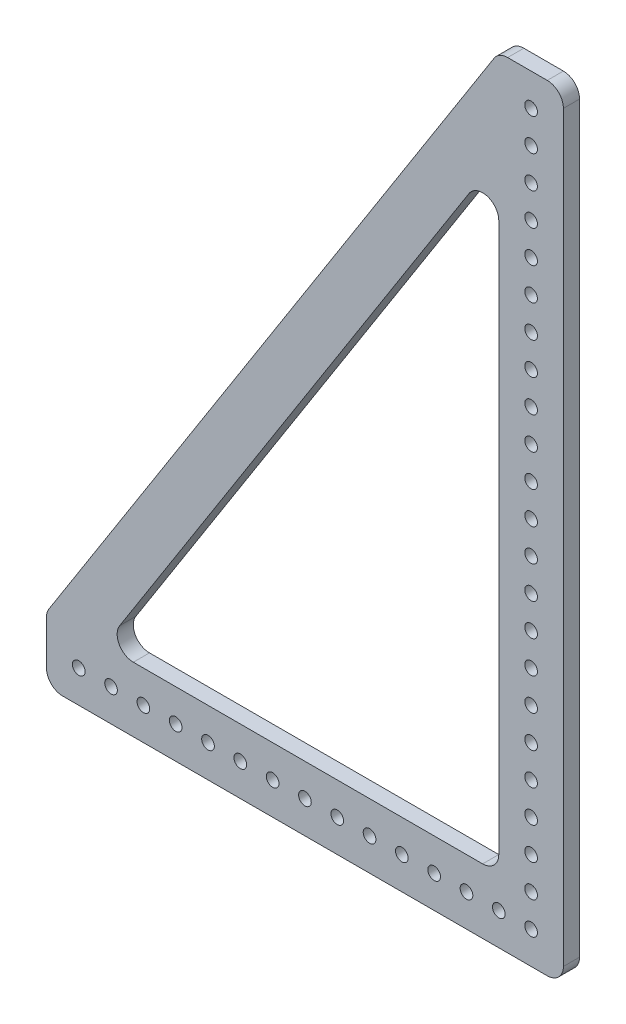
SolidWorks part; units mm, degrees
material "6061-T6 (SS)"
ref_plane "Front Plane" through (0, 0, 0) normal (0, 0, 1) x (1, 0, 0)
ref_plane "Top Plane" through (0, 0, 0) normal (0, 1, 0) x (1, 0, 0)
ref_plane "Right Plane" through (0, 0, 0) normal (1, 0, 0) x (0, 0, -1)
sketch "Sketch1" plane through (0, 0, 0) normal (0, 0, 1) x (1, 0, 0)
  line L0 (0, 25.4) -> (177.8, 304.8)
  line L1 (177.8, 304.8) -> (203.2, 304.8)
  line L2 (0, 25.4) -> (0, 0)
  line L3 (0, 0) -> (203.2, 0)
  line L4 (203.2, 304.8) -> (203.2, 0)
  dimension "D1" = 304.8
  dimension "D2" = 203.2
  dimension "D3" = 25.4
  dimension "D4" = 25.4
extrude "Boss-Extrude1" add sketch "Sketch1" along normal blind 6.35
sketch "Sketch2" plane through (0, 0, 6.35) normal (0, 0, 1) x (1, 0, 0)
  line L0 (0, 0) -> (203.2, 0) construction
  line L1 (203.2, 0) -> (203.2, 304.8) construction
  line L2 (22.5801, 25.4) -> (177.8, 25.4)
  line L3 (177.8, 25.4) -> (177.8, 269.3169)
  line L4 (177.8, 269.3169) -> (22.5801, 25.4)
  line L5 (177.8, 304.8) -> (0, 25.4) construction
  circle A0 centre (190.5, 12.7) radius 2.4892
  circle A1 centre (177.8, 12.7) radius 2.4892
  circle A2 centre (165.1, 12.7) radius 2.4892
  circle A3 centre (152.4, 12.7) radius 2.4892
  circle A4 centre (139.7, 12.7) radius 2.4892
  circle A5 centre (127, 12.7) radius 2.4892
  circle A6 centre (114.3, 12.7) radius 2.4892
  circle A67 centre (190.5, 25.4) radius 2.4892
  circle A68 centre (190.5, 38.1) radius 2.4892
  circle A69 centre (190.5, 50.8) radius 2.4892
  circle A70 centre (190.5, 63.5) radius 2.4892
  circle A71 centre (190.5, 76.2) radius 2.4892
  circle A72 centre (190.5, 88.9) radius 2.4892
  circle A73 centre (190.5, 101.6) radius 2.4892
  circle A74 centre (190.5, 114.3) radius 2.4892
  circle A75 centre (190.5, 127) radius 2.4892
  circle A76 centre (190.5, 139.7) radius 2.4892
  circle A77 centre (190.5, 152.4) radius 2.4892
  circle A84 centre (190.5, 165.1) radius 2.4892
  circle A91 centre (190.5, 177.8) radius 2.4892
  circle A98 centre (190.5, 190.5) radius 2.4892
  circle A105 centre (190.5, 203.2) radius 2.4892
  circle A112 centre (190.5, 215.9) radius 2.4892
  circle A119 centre (190.5, 228.6) radius 2.4892
  circle A126 centre (190.5, 241.3) radius 2.4892
  circle A133 centre (190.5, 254) radius 2.4892
  circle A140 centre (190.5, 266.7) radius 2.4892
  circle A147 centre (190.5, 279.4) radius 2.4892
  circle A154 centre (190.5, 292.1) radius 2.4892
  circle A161 centre (177.8, 152.4) radius 2.4892 [skipped]
  circle A162 centre (165.1, 152.4) radius 2.4892 [skipped]
  circle A163 centre (152.4, 152.4) radius 2.4892 [skipped]
  circle A164 centre (139.7, 152.4) radius 2.4892 [skipped]
  circle A165 centre (127, 152.4) radius 2.4892 [skipped]
  circle A166 centre (114.3, 152.4) radius 2.4892 [skipped]
  circle A167 centre (177.8, 165.1) radius 2.4892 [skipped]
  circle A168 centre (165.1, 165.1) radius 2.4892 [skipped]
  circle A169 centre (152.4, 165.1) radius 2.4892 [skipped]
  circle A170 centre (139.7, 165.1) radius 2.4892 [skipped]
  circle A171 centre (127, 165.1) radius 2.4892 [skipped]
  circle A172 centre (114.3, 165.1) radius 2.4892 [skipped]
  circle A173 centre (177.8, 177.8) radius 2.4892 [skipped]
  circle A174 centre (165.1, 177.8) radius 2.4892 [skipped]
  circle A175 centre (152.4, 177.8) radius 2.4892 [skipped]
  circle A176 centre (139.7, 177.8) radius 2.4892 [skipped]
  circle A177 centre (127, 177.8) radius 2.4892 [skipped]
  circle A178 centre (114.3, 177.8) radius 2.4892 [skipped]
  circle A179 centre (177.8, 190.5) radius 2.4892 [skipped]
  circle A180 centre (165.1, 190.5) radius 2.4892 [skipped]
  circle A181 centre (152.4, 190.5) radius 2.4892 [skipped]
  circle A182 centre (139.7, 190.5) radius 2.4892 [skipped]
  circle A183 centre (127, 190.5) radius 2.4892 [skipped]
  circle A184 centre (114.3, 190.5) radius 2.4892 [skipped]
  circle A185 centre (177.8, 203.2) radius 2.4892 [skipped]
  circle A186 centre (165.1, 203.2) radius 2.4892 [skipped]
  circle A187 centre (152.4, 203.2) radius 2.4892 [skipped]
  circle A188 centre (139.7, 203.2) radius 2.4892 [skipped]
  circle A189 centre (127, 203.2) radius 2.4892 [skipped]
  circle A190 centre (114.3, 203.2) radius 2.4892 [skipped]
  circle A191 centre (177.8, 215.9) radius 2.4892 [skipped]
  circle A192 centre (165.1, 215.9) radius 2.4892 [skipped]
  circle A193 centre (152.4, 215.9) radius 2.4892 [skipped]
  circle A194 centre (139.7, 215.9) radius 2.4892 [skipped]
  circle A195 centre (127, 215.9) radius 2.4892 [skipped]
  circle A196 centre (114.3, 215.9) radius 2.4892 [skipped]
  circle A197 centre (177.8, 228.6) radius 2.4892 [skipped]
  circle A198 centre (165.1, 228.6) radius 2.4892 [skipped]
  circle A199 centre (152.4, 228.6) radius 2.4892 [skipped]
  circle A200 centre (139.7, 228.6) radius 2.4892 [skipped]
  circle A201 centre (127, 228.6) radius 2.4892 [skipped]
  circle A202 centre (114.3, 228.6) radius 2.4892 [skipped]
  circle A203 centre (177.8, 241.3) radius 2.4892 [skipped]
  circle A204 centre (165.1, 241.3) radius 2.4892 [skipped]
  circle A205 centre (152.4, 241.3) radius 2.4892 [skipped]
  circle A206 centre (139.7, 241.3) radius 2.4892 [skipped]
  circle A207 centre (127, 241.3) radius 2.4892 [skipped]
  circle A208 centre (114.3, 241.3) radius 2.4892 [skipped]
  circle A209 centre (177.8, 254) radius 2.4892 [skipped]
  circle A210 centre (165.1, 254) radius 2.4892 [skipped]
  circle A211 centre (152.4, 254) radius 2.4892 [skipped]
  circle A212 centre (139.7, 254) radius 2.4892 [skipped]
  circle A213 centre (127, 254) radius 2.4892 [skipped]
  circle A214 centre (114.3, 254) radius 2.4892 [skipped]
  circle A215 centre (177.8, 266.7) radius 2.4892 [skipped]
  circle A216 centre (165.1, 266.7) radius 2.4892 [skipped]
  circle A217 centre (152.4, 266.7) radius 2.4892 [skipped]
  circle A218 centre (139.7, 266.7) radius 2.4892 [skipped]
  circle A219 centre (127, 266.7) radius 2.4892 [skipped]
  circle A220 centre (114.3, 266.7) radius 2.4892 [skipped]
  circle A221 centre (177.8, 279.4) radius 2.4892 [skipped]
  circle A222 centre (165.1, 279.4) radius 2.4892 [skipped]
  circle A223 centre (152.4, 279.4) radius 2.4892 [skipped]
  circle A224 centre (139.7, 279.4) radius 2.4892 [skipped]
  circle A225 centre (127, 279.4) radius 2.4892 [skipped]
  circle A226 centre (114.3, 279.4) radius 2.4892 [skipped]
  circle A227 centre (177.8, 292.1) radius 2.4892 [skipped]
  circle A228 centre (165.1, 292.1) radius 2.4892 [skipped]
  circle A229 centre (152.4, 292.1) radius 2.4892 [skipped]
  circle A230 centre (139.7, 292.1) radius 2.4892 [skipped]
  circle A231 centre (127, 292.1) radius 2.4892 [skipped]
  circle A232 centre (114.3, 292.1) radius 2.4892 [skipped]
  circle A233 centre (165.1, 25.4) radius 2.4892 construction
  circle A234 centre (152.4, 25.4) radius 2.4892 construction
  circle A235 centre (139.7, 25.4) radius 2.4892 construction
  circle A236 centre (127, 25.4) radius 2.4892 construction
  circle A237 centre (114.3, 25.4) radius 2.4892 construction
  circle A238 centre (177.8, 38.1) radius 2.4892 construction
  circle A239 centre (165.1, 38.1) radius 2.4892 construction
  circle A240 centre (152.4, 38.1) radius 2.4892 construction
  circle A241 centre (139.7, 38.1) radius 2.4892 construction
  circle A242 centre (127, 38.1) radius 2.4892 construction
  circle A243 centre (114.3, 38.1) radius 2.4892 construction
  circle A244 centre (177.8, 50.8) radius 2.4892 construction
  circle A245 centre (165.1, 50.8) radius 2.4892 construction
  circle A246 centre (152.4, 50.8) radius 2.4892 construction
  circle A247 centre (139.7, 50.8) radius 2.4892 construction
  circle A248 centre (127, 50.8) radius 2.4892 construction
  circle A249 centre (114.3, 50.8) radius 2.4892 construction
  circle A250 centre (177.8, 63.5) radius 2.4892 construction
  circle A251 centre (165.1, 63.5) radius 2.4892 construction
  circle A252 centre (152.4, 63.5) radius 2.4892 construction
  circle A253 centre (139.7, 63.5) radius 2.4892 construction
  circle A254 centre (127, 63.5) radius 2.4892 construction
  circle A255 centre (114.3, 63.5) radius 2.4892 construction
  circle A256 centre (177.8, 76.2) radius 2.4892 construction
  circle A257 centre (165.1, 76.2) radius 2.4892 construction
  circle A258 centre (152.4, 76.2) radius 2.4892 construction
  circle A259 centre (139.7, 76.2) radius 2.4892 construction
  circle A260 centre (127, 76.2) radius 2.4892 construction
  circle A261 centre (114.3, 76.2) radius 2.4892 construction
  circle A262 centre (177.8, 88.9) radius 2.4892 construction
  circle A263 centre (165.1, 88.9) radius 2.4892 construction
  circle A264 centre (152.4, 88.9) radius 2.4892 construction
  circle A265 centre (139.7, 88.9) radius 2.4892 construction
  circle A266 centre (127, 88.9) radius 2.4892 construction
  circle A267 centre (114.3, 88.9) radius 2.4892 construction
  circle A268 centre (177.8, 101.6) radius 2.4892 construction
  circle A269 centre (165.1, 101.6) radius 2.4892 construction
  circle A270 centre (152.4, 101.6) radius 2.4892 construction
  circle A271 centre (139.7, 101.6) radius 2.4892 construction
  circle A272 centre (127, 101.6) radius 2.4892 construction
  circle A273 centre (114.3, 101.6) radius 2.4892 construction
  circle A274 centre (177.8, 114.3) radius 2.4892 construction
  circle A275 centre (165.1, 114.3) radius 2.4892 construction
  circle A276 centre (152.4, 114.3) radius 2.4892 construction
  circle A277 centre (139.7, 114.3) radius 2.4892 construction
  circle A278 centre (127, 114.3) radius 2.4892 construction
  circle A279 centre (114.3, 114.3) radius 2.4892 construction
  circle A280 centre (177.8, 127) radius 2.4892 construction
  circle A281 centre (165.1, 127) radius 2.4892 construction
  circle A282 centre (152.4, 127) radius 2.4892 construction
  circle A283 centre (139.7, 127) radius 2.4892 construction
  circle A284 centre (127, 127) radius 2.4892 construction
  circle A285 centre (114.3, 127) radius 2.4892 construction
  circle A286 centre (177.8, 139.7) radius 2.4892 construction
  circle A287 centre (165.1, 139.7) radius 2.4892 construction
  circle A288 centre (152.4, 139.7) radius 2.4892 construction
  circle A289 centre (139.7, 139.7) radius 2.4892 construction
  circle A290 centre (127, 139.7) radius 2.4892 construction
  circle A291 centre (114.3, 139.7) radius 2.4892 construction
  circle A292 centre (177.8, 25.4) radius 2.4892 construction
  circle A293 centre (101.6, 12.7) radius 2.4892
  circle A294 centre (88.9, 12.7) radius 2.4892
  circle A295 centre (76.2, 12.7) radius 2.4892
  circle A296 centre (63.5, 12.7) radius 2.4892
  circle A297 centre (50.8, 12.7) radius 2.4892
  circle A298 centre (38.1, 12.7) radius 2.4892
  circle A299 centre (25.4, 12.7) radius 2.4892
  circle A300 centre (12.7, 12.7) radius 2.4892
  circle A477 centre (101.6, 25.4) radius 2.4892 [skipped]
  circle A478 centre (88.9, 25.4) radius 2.4892 [skipped]
  circle A479 centre (76.2, 25.4) radius 2.4892 [skipped]
  circle A480 centre (63.5, 25.4) radius 2.4892 [skipped]
  circle A481 centre (50.8, 25.4) radius 2.4892 [skipped]
  circle A482 centre (38.1, 25.4) radius 2.4892 [skipped]
  circle A483 centre (25.4, 25.4) radius 2.4892 [skipped]
  circle A484 centre (12.7, 25.4) radius 2.4892 [skipped]
  circle A485 centre (101.6, 38.1) radius 2.4892 [skipped]
  circle A486 centre (88.9, 38.1) radius 2.4892 [skipped]
  circle A487 centre (76.2, 38.1) radius 2.4892 [skipped]
  circle A488 centre (63.5, 38.1) radius 2.4892 [skipped]
  circle A489 centre (50.8, 38.1) radius 2.4892 [skipped]
  circle A490 centre (38.1, 38.1) radius 2.4892 [skipped]
  circle A491 centre (25.4, 38.1) radius 2.4892 [skipped]
  circle A492 centre (12.7, 38.1) radius 2.4892 [skipped]
  circle A493 centre (101.6, 50.8) radius 2.4892 [skipped]
  circle A494 centre (88.9, 50.8) radius 2.4892 [skipped]
  circle A495 centre (76.2, 50.8) radius 2.4892 [skipped]
  circle A496 centre (63.5, 50.8) radius 2.4892 [skipped]
  circle A497 centre (50.8, 50.8) radius 2.4892 [skipped]
  circle A498 centre (38.1, 50.8) radius 2.4892 [skipped]
  circle A499 centre (25.4, 50.8) radius 2.4892 [skipped]
  circle A500 centre (12.7, 50.8) radius 2.4892 [skipped]
  circle A501 centre (101.6, 63.5) radius 2.4892 [skipped]
  circle A502 centre (88.9, 63.5) radius 2.4892 [skipped]
  circle A503 centre (76.2, 63.5) radius 2.4892 [skipped]
  circle A504 centre (63.5, 63.5) radius 2.4892 [skipped]
  circle A505 centre (50.8, 63.5) radius 2.4892 [skipped]
  circle A506 centre (38.1, 63.5) radius 2.4892 [skipped]
  circle A507 centre (25.4, 63.5) radius 2.4892 [skipped]
  circle A508 centre (12.7, 63.5) radius 2.4892 [skipped]
  circle A509 centre (101.6, 76.2) radius 2.4892 [skipped]
  circle A510 centre (88.9, 76.2) radius 2.4892 [skipped]
  circle A511 centre (76.2, 76.2) radius 2.4892 [skipped]
  circle A512 centre (63.5, 76.2) radius 2.4892 [skipped]
  circle A513 centre (50.8, 76.2) radius 2.4892 [skipped]
  circle A514 centre (38.1, 76.2) radius 2.4892 [skipped]
  circle A515 centre (25.4, 76.2) radius 2.4892 [skipped]
  circle A516 centre (12.7, 76.2) radius 2.4892 [skipped]
  circle A517 centre (101.6, 88.9) radius 2.4892 [skipped]
  circle A518 centre (88.9, 88.9) radius 2.4892 [skipped]
  circle A519 centre (76.2, 88.9) radius 2.4892 [skipped]
  circle A520 centre (63.5, 88.9) radius 2.4892 [skipped]
  circle A521 centre (50.8, 88.9) radius 2.4892 [skipped]
  circle A522 centre (38.1, 88.9) radius 2.4892 [skipped]
  circle A523 centre (25.4, 88.9) radius 2.4892 [skipped]
  circle A524 centre (12.7, 88.9) radius 2.4892 [skipped]
  circle A525 centre (101.6, 101.6) radius 2.4892 [skipped]
  circle A526 centre (88.9, 101.6) radius 2.4892 [skipped]
  circle A527 centre (76.2, 101.6) radius 2.4892 [skipped]
  circle A528 centre (63.5, 101.6) radius 2.4892 [skipped]
  circle A529 centre (50.8, 101.6) radius 2.4892 [skipped]
  circle A530 centre (38.1, 101.6) radius 2.4892 [skipped]
  circle A531 centre (25.4, 101.6) radius 2.4892 [skipped]
  circle A532 centre (12.7, 101.6) radius 2.4892 [skipped]
  circle A533 centre (101.6, 114.3) radius 2.4892 [skipped]
  circle A534 centre (88.9, 114.3) radius 2.4892 [skipped]
  circle A535 centre (76.2, 114.3) radius 2.4892 [skipped]
  circle A536 centre (63.5, 114.3) radius 2.4892 [skipped]
  circle A537 centre (50.8, 114.3) radius 2.4892 [skipped]
  circle A538 centre (38.1, 114.3) radius 2.4892 [skipped]
  circle A539 centre (25.4, 114.3) radius 2.4892 [skipped]
  circle A540 centre (12.7, 114.3) radius 2.4892 [skipped]
  circle A541 centre (101.6, 127) radius 2.4892 [skipped]
  circle A542 centre (88.9, 127) radius 2.4892 [skipped]
  circle A543 centre (76.2, 127) radius 2.4892 [skipped]
  circle A544 centre (63.5, 127) radius 2.4892 [skipped]
  circle A545 centre (50.8, 127) radius 2.4892 [skipped]
  circle A546 centre (38.1, 127) radius 2.4892 [skipped]
  circle A547 centre (25.4, 127) radius 2.4892 [skipped]
  circle A548 centre (12.7, 127) radius 2.4892 [skipped]
  circle A549 centre (101.6, 139.7) radius 2.4892 [skipped]
  circle A550 centre (88.9, 139.7) radius 2.4892 [skipped]
  circle A551 centre (76.2, 139.7) radius 2.4892 [skipped]
  circle A552 centre (63.5, 139.7) radius 2.4892 [skipped]
  circle A553 centre (50.8, 139.7) radius 2.4892 [skipped]
  circle A554 centre (38.1, 139.7) radius 2.4892 [skipped]
  circle A555 centre (25.4, 139.7) radius 2.4892 [skipped]
  circle A556 centre (12.7, 139.7) radius 2.4892 [skipped]
  circle A557 centre (101.6, 152.4) radius 2.4892 [skipped]
  circle A558 centre (88.9, 152.4) radius 2.4892 [skipped]
  circle A559 centre (76.2, 152.4) radius 2.4892 [skipped]
  circle A560 centre (63.5, 152.4) radius 2.4892 [skipped]
  circle A561 centre (50.8, 152.4) radius 2.4892 [skipped]
  circle A562 centre (38.1, 152.4) radius 2.4892 [skipped]
  circle A563 centre (25.4, 152.4) radius 2.4892 [skipped]
  circle A564 centre (12.7, 152.4) radius 2.4892 [skipped]
  circle A565 centre (101.6, 165.1) radius 2.4892 [skipped]
  circle A566 centre (88.9, 165.1) radius 2.4892 [skipped]
  circle A567 centre (76.2, 165.1) radius 2.4892 [skipped]
  circle A568 centre (63.5, 165.1) radius 2.4892 [skipped]
  circle A569 centre (50.8, 165.1) radius 2.4892 [skipped]
  circle A570 centre (38.1, 165.1) radius 2.4892 [skipped]
  circle A571 centre (25.4, 165.1) radius 2.4892 [skipped]
  circle A572 centre (12.7, 165.1) radius 2.4892 [skipped]
  circle A573 centre (101.6, 177.8) radius 2.4892 [skipped]
  circle A574 centre (88.9, 177.8) radius 2.4892 [skipped]
  circle A575 centre (76.2, 177.8) radius 2.4892 [skipped]
  circle A576 centre (63.5, 177.8) radius 2.4892 [skipped]
  circle A577 centre (50.8, 177.8) radius 2.4892 [skipped]
  circle A578 centre (38.1, 177.8) radius 2.4892 [skipped]
  circle A579 centre (25.4, 177.8) radius 2.4892 [skipped]
  circle A580 centre (12.7, 177.8) radius 2.4892 [skipped]
  circle A581 centre (101.6, 190.5) radius 2.4892 [skipped]
  circle A582 centre (88.9, 190.5) radius 2.4892 [skipped]
  circle A583 centre (76.2, 190.5) radius 2.4892 [skipped]
  circle A584 centre (63.5, 190.5) radius 2.4892 [skipped]
  circle A585 centre (50.8, 190.5) radius 2.4892 [skipped]
  circle A586 centre (38.1, 190.5) radius 2.4892 [skipped]
  circle A587 centre (25.4, 190.5) radius 2.4892 [skipped]
  circle A588 centre (12.7, 190.5) radius 2.4892 [skipped]
  circle A589 centre (101.6, 203.2) radius 2.4892 [skipped]
  circle A590 centre (88.9, 203.2) radius 2.4892 [skipped]
  circle A591 centre (76.2, 203.2) radius 2.4892 [skipped]
  circle A592 centre (63.5, 203.2) radius 2.4892 [skipped]
  circle A593 centre (50.8, 203.2) radius 2.4892 [skipped]
  circle A594 centre (38.1, 203.2) radius 2.4892 [skipped]
  circle A595 centre (25.4, 203.2) radius 2.4892 [skipped]
  circle A596 centre (12.7, 203.2) radius 2.4892 [skipped]
  circle A597 centre (101.6, 215.9) radius 2.4892 [skipped]
  circle A598 centre (88.9, 215.9) radius 2.4892 [skipped]
  circle A599 centre (76.2, 215.9) radius 2.4892 [skipped]
  circle A600 centre (63.5, 215.9) radius 2.4892 [skipped]
  circle A601 centre (50.8, 215.9) radius 2.4892 [skipped]
  circle A602 centre (38.1, 215.9) radius 2.4892 [skipped]
  circle A603 centre (25.4, 215.9) radius 2.4892 [skipped]
  circle A604 centre (12.7, 215.9) radius 2.4892 [skipped]
  circle A605 centre (101.6, 228.6) radius 2.4892 [skipped]
  circle A606 centre (88.9, 228.6) radius 2.4892 [skipped]
  circle A607 centre (76.2, 228.6) radius 2.4892 [skipped]
  circle A608 centre (63.5, 228.6) radius 2.4892 [skipped]
  circle A609 centre (50.8, 228.6) radius 2.4892 [skipped]
  circle A610 centre (38.1, 228.6) radius 2.4892 [skipped]
  circle A611 centre (25.4, 228.6) radius 2.4892 [skipped]
  circle A612 centre (12.7, 228.6) radius 2.4892 [skipped]
  circle A613 centre (101.6, 241.3) radius 2.4892 [skipped]
  circle A614 centre (88.9, 241.3) radius 2.4892 [skipped]
  circle A615 centre (76.2, 241.3) radius 2.4892 [skipped]
  circle A616 centre (63.5, 241.3) radius 2.4892 [skipped]
  circle A617 centre (50.8, 241.3) radius 2.4892 [skipped]
  circle A618 centre (38.1, 241.3) radius 2.4892 [skipped]
  circle A619 centre (25.4, 241.3) radius 2.4892 [skipped]
  circle A620 centre (12.7, 241.3) radius 2.4892 [skipped]
  circle A621 centre (101.6, 254) radius 2.4892 [skipped]
  circle A622 centre (88.9, 254) radius 2.4892 [skipped]
  circle A623 centre (76.2, 254) radius 2.4892 [skipped]
  circle A624 centre (63.5, 254) radius 2.4892 [skipped]
  circle A625 centre (50.8, 254) radius 2.4892 [skipped]
  circle A626 centre (38.1, 254) radius 2.4892 [skipped]
  circle A627 centre (25.4, 254) radius 2.4892 [skipped]
  circle A628 centre (12.7, 254) radius 2.4892 [skipped]
  circle A629 centre (101.6, 266.7) radius 2.4892 [skipped]
  circle A630 centre (88.9, 266.7) radius 2.4892 [skipped]
  circle A631 centre (76.2, 266.7) radius 2.4892 [skipped]
  circle A632 centre (63.5, 266.7) radius 2.4892 [skipped]
  circle A633 centre (50.8, 266.7) radius 2.4892 [skipped]
  circle A634 centre (38.1, 266.7) radius 2.4892 [skipped]
  circle A635 centre (25.4, 266.7) radius 2.4892 [skipped]
  circle A636 centre (12.7, 266.7) radius 2.4892 [skipped]
  circle A637 centre (101.6, 279.4) radius 2.4892 [skipped]
  circle A638 centre (88.9, 279.4) radius 2.4892 [skipped]
  circle A639 centre (76.2, 279.4) radius 2.4892 [skipped]
  circle A640 centre (63.5, 279.4) radius 2.4892 [skipped]
  circle A641 centre (50.8, 279.4) radius 2.4892 [skipped]
  circle A642 centre (38.1, 279.4) radius 2.4892 [skipped]
  circle A643 centre (25.4, 279.4) radius 2.4892 [skipped]
  circle A644 centre (12.7, 279.4) radius 2.4892 [skipped]
  circle A645 centre (101.6, 292.1) radius 2.4892 [skipped]
  circle A646 centre (88.9, 292.1) radius 2.4892 [skipped]
  circle A647 centre (76.2, 292.1) radius 2.4892 [skipped]
  circle A648 centre (63.5, 292.1) radius 2.4892 [skipped]
  circle A649 centre (50.8, 292.1) radius 2.4892 [skipped]
  circle A650 centre (38.1, 292.1) radius 2.4892 [skipped]
  circle A651 centre (25.4, 292.1) radius 2.4892 [skipped]
  circle A652 centre (12.7, 292.1) radius 2.4892 [skipped]
  dimension "D1" = 12.7
  dimension "D2" = 12.7
  dimension "D3" = 4.9784
  dimension "D6" = 12.7
  dimension "D7" = 12.7
  dimension "D8" = 25.4
  dimension "D9" = 25.4
  dimension "D10" = 19.05
  dimension "D5" = 15
  dimension "D4" = 23
extrude "Cut-Extrude1" cut sketch "Sketch2" against normal through all
fillet "Fillet1" radius 6.35 8 edges at (203.2, 0, 3.175) (0, 25.4, 3.175) (177.8, 304.8, 3.175) (203.2, 304.8, 3.175) (0, 0, 3.175) (177.8, 25.4, 3.175) (177.8, 269.3169, 3.175) (22.5801, 25.4, 3.175)
